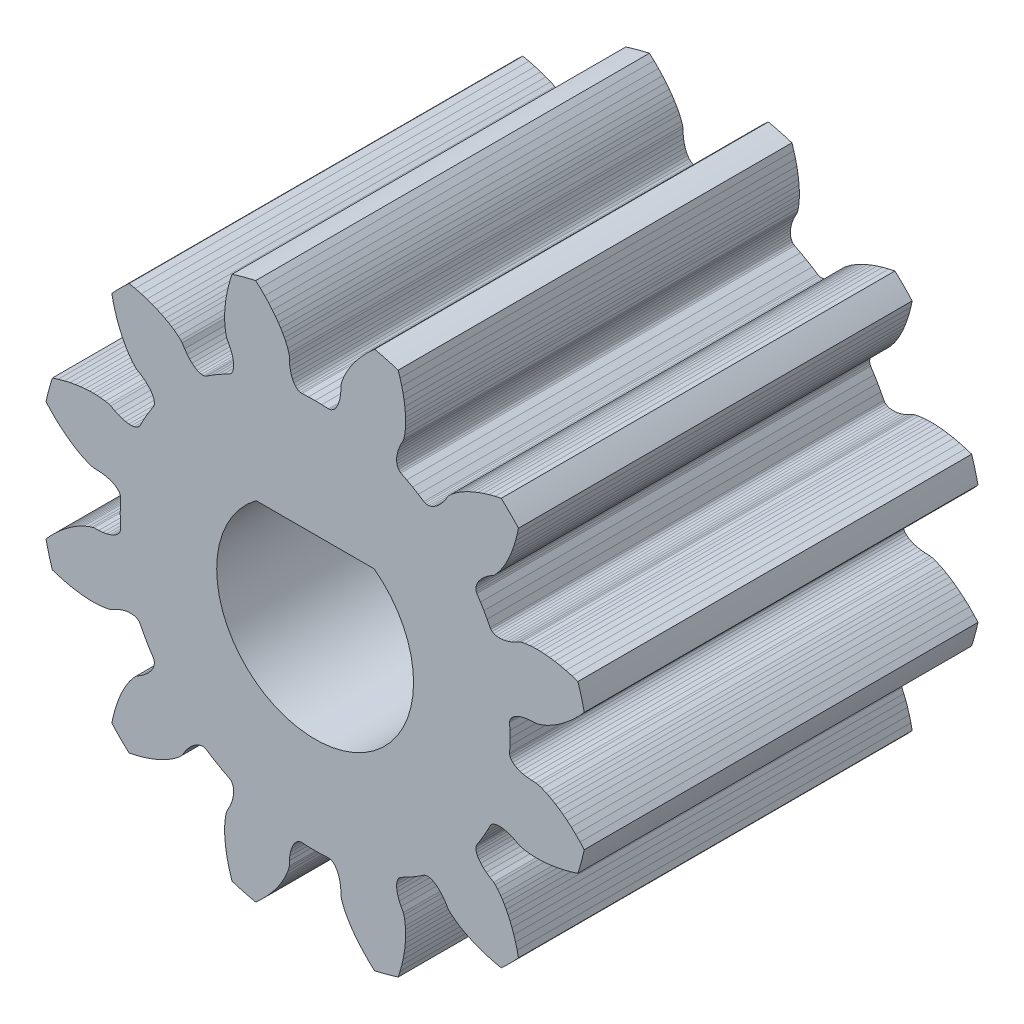
SolidWorks part; units mm, degrees
ref_plane "Front Plane" through (0, 0, 0) normal (0, 0, 1) x (1, 0, 0)
ref_plane "Top Plane" through (0, 0, 0) normal (0, 1, 0) x (1, 0, 0)
ref_plane "Right Plane" through (0, 0, 0) normal (1, 0, 0) x (0, 0, -1)
sketch "Model" plane through (0, 0, 0) normal (0, 0, 1) x (1, 0, 0)
  line L0 (30.8694, -4.5708) -> (30.9098, -4.4161)
  line L1 (30.9098, -4.4161) -> (30.9538, -4.2725)
  line L2 (30.9538, -4.2725) -> (31.0003, -4.1408)
  line L3 (31.0003, -4.1408) -> (31.0488, -4.0198)
  line L4 (31.0488, -4.0198) -> (31.0977, -3.9112)
  line L5 (31.0977, -3.9112) -> (31.1475, -3.8119)
  line L6 (31.1475, -3.8119) -> (31.1956, -3.7252)
  line L7 (31.1956, -3.7252) -> (31.2429, -3.6478)
  line L8 (31.2429, -3.6478) -> (31.2875, -3.5813)
  line L9 (31.2875, -3.5813) -> (31.3671, -3.477)
  line L10 (31.3671, -3.477) -> (31.4285, -3.4089)
  line L11 (31.4285, -3.4089) -> (31.466, -3.3746)
  line L12 (31.466, -3.3746) -> (31.5668, -3.3141)
  line L13 (31.5668, -3.3141) -> (31.6547, -3.2516)
  line L14 (31.6547, -3.2516) -> (31.7296, -3.1879)
  line L15 (31.7296, -3.1879) -> (31.7917, -3.1241)
  line L16 (31.7917, -3.1241) -> (31.841, -3.0611)
  line L17 (31.841, -3.0611) -> (31.8779, -2.9999)
  line L18 (31.8779, -2.9999) -> (31.9025, -2.9414)
  line L19 (31.9025, -2.9414) -> (31.9152, -2.8864)
  line L20 (31.9152, -2.8864) -> (31.9163, -2.836)
  line L21 (31.9163, -2.836) -> (31.9062, -2.7909)
  line L22 (31.9062, -2.7909) -> (31.8916, -2.7611)
  line L23 (31.8916, -2.7611) -> (31.8003, -2.6202)
  line L24 (31.8003, -2.6202) -> (31.7132, -2.475)
  line L25 (31.7132, -2.475) -> (31.631, -2.327)
  line L26 (31.631, -2.327) -> (31.5546, -2.1774)
  line L27 (31.5546, -2.1774) -> (31.5361, -2.1499)
  line L28 (31.5361, -2.1499) -> (31.5021, -2.1186)
  line L29 (31.5021, -2.1186) -> (31.4579, -2.0943)
  line L30 (31.4579, -2.0943) -> (31.404, -2.0778)
  line L31 (31.404, -2.0778) -> (31.341, -2.0699)
  line L32 (31.341, -2.0699) -> (31.2695, -2.0712)
  line L33 (31.2695, -2.0712) -> (31.1903, -2.0825)
  line L34 (31.1903, -2.0825) -> (31.104, -2.1043)
  line L35 (31.104, -2.1043) -> (31.0114, -2.1374)
  line L36 (31.0114, -2.1374) -> (30.9133, -2.1822)
  line L37 (30.9133, -2.1822) -> (30.8106, -2.2393)
  line L38 (30.8106, -2.2393) -> (30.762, -2.2546)
  line L39 (30.762, -2.2546) -> (30.6724, -2.2738)
  line L40 (30.6724, -2.2738) -> (30.5422, -2.2905)
  line L41 (30.5422, -2.2905) -> (30.4624, -2.2959)
  line L42 (30.4624, -2.2959) -> (30.3717, -2.2981)
  line L43 (30.3717, -2.2981) -> (30.2725, -2.2965)
  line L44 (30.2725, -2.2965) -> (30.1616, -2.2899)
  line L45 (30.1616, -2.2899) -> (30.0431, -2.278)
  line L46 (30.0431, -2.278) -> (29.9141, -2.2595)
  line L47 (29.9141, -2.2595) -> (29.7768, -2.2339)
  line L48 (29.7768, -2.2339) -> (29.6305, -2.2002)
  line L49 (29.6305, -2.2002) -> (29.4762, -2.1578)
  line L50 (29.4762, -2.1578) -> (29.3255, -2.1096)
  line L51 (29.1649, -1.5103) -> (29.2713, -1.3932)
  line L52 (29.2713, -1.3932) -> (29.3837, -1.2793)
  line L53 (29.3837, -1.2793) -> (29.4936, -1.177)
  line L54 (29.4936, -1.177) -> (29.5997, -1.0861)
  line L55 (29.5997, -1.0861) -> (29.7022, -1.0056)
  line L56 (29.7022, -1.0056) -> (29.7988, -0.9361)
  line L57 (29.7988, -0.9361) -> (29.8916, -0.875)
  line L58 (29.8916, -0.875) -> (29.9767, -0.8239)
  line L59 (29.9767, -0.8239) -> (30.0563, -0.7805)
  line L60 (30.0563, -0.7805) -> (30.1282, -0.7452)
  line L61 (30.1282, -0.7452) -> (30.2493, -0.6947)
  line L62 (30.2493, -0.6947) -> (30.3365, -0.6665)
  line L63 (30.3365, -0.6665) -> (30.3862, -0.6555)
  line L64 (30.3862, -0.6555) -> (30.5037, -0.6535)
  line L65 (30.5037, -0.6535) -> (30.611, -0.6433)
  line L66 (30.611, -0.6433) -> (30.7078, -0.6256)
  line L67 (30.7078, -0.6256) -> (30.7934, -0.6014)
  line L68 (30.7934, -0.6014) -> (30.8677, -0.5716)
  line L69 (30.8677, -0.5716) -> (30.9302, -0.537)
  line L70 (30.9302, -0.537) -> (30.9808, -0.4986)
  line L71 (30.9808, -0.4986) -> (31.0192, -0.4573)
  line L72 (31.0192, -0.4573) -> (31.0454, -0.4142)
  line L73 (31.0454, -0.4142) -> (31.0592, -0.3701)
  line L74 (31.0592, -0.3701) -> (31.0614, -0.337)
  line L75 (31.0614, -0.337) -> (31.0529, -0.1693)
  line L76 (31.0529, -0.1693) -> (31.05, 0)
  line L77 (31.05, 0) -> (31.0529, 0.1693)
  line L78 (31.0529, 0.1693) -> (31.0614, 0.337)
  line L79 (31.0614, 0.337) -> (31.0592, 0.3701)
  line L80 (31.0592, 0.3701) -> (31.0454, 0.4142)
  line L81 (31.0454, 0.4142) -> (31.0192, 0.4573)
  line L82 (31.0192, 0.4573) -> (30.9808, 0.4986)
  line L83 (30.9808, 0.4986) -> (30.9302, 0.537)
  line L84 (30.9302, 0.537) -> (30.8677, 0.5716)
  line L85 (30.8677, 0.5716) -> (30.7934, 0.6014)
  line L86 (30.7934, 0.6014) -> (30.7078, 0.6256)
  line L87 (30.7078, 0.6256) -> (30.611, 0.6433)
  line L88 (30.611, 0.6433) -> (30.5037, 0.6535)
  line L89 (30.5037, 0.6535) -> (30.3862, 0.6555)
  line L90 (30.3862, 0.6555) -> (30.3365, 0.6665)
  line L91 (30.3365, 0.6665) -> (30.2493, 0.6947)
  line L92 (30.2493, 0.6947) -> (30.1282, 0.7452)
  line L93 (30.1282, 0.7452) -> (30.0563, 0.7805)
  line L94 (30.0563, 0.7805) -> (29.9767, 0.8239)
  line L95 (29.9767, 0.8239) -> (29.8916, 0.875)
  line L96 (29.8916, 0.875) -> (29.7988, 0.9361)
  line L97 (29.7988, 0.9361) -> (29.7022, 1.0056)
  line L98 (29.7022, 1.0056) -> (29.5997, 1.0861)
  line L99 (29.5997, 1.0861) -> (29.4936, 1.177)
  line L100 (29.4936, 1.177) -> (29.3837, 1.2793)
  line L101 (29.3837, 1.2793) -> (29.2713, 1.3932)
  line L102 (29.2713, 1.3932) -> (29.1649, 1.5103)
  line L103 (29.3255, 2.1096) -> (29.4762, 2.1578)
  line L104 (29.4762, 2.1578) -> (29.6305, 2.2002)
  line L105 (29.6305, 2.2002) -> (29.7768, 2.2339)
  line L106 (29.7768, 2.2339) -> (29.9141, 2.2595)
  line L107 (29.9141, 2.2595) -> (30.0431, 2.278)
  line L108 (30.0431, 2.278) -> (30.1616, 2.2899)
  line L109 (30.1616, 2.2899) -> (30.2725, 2.2965)
  line L110 (30.2725, 2.2965) -> (30.3717, 2.2981)
  line L111 (30.3717, 2.2981) -> (30.4624, 2.2959)
  line L112 (30.4624, 2.2959) -> (30.5422, 2.2905)
  line L113 (30.5422, 2.2905) -> (30.6724, 2.2738)
  line L114 (30.6724, 2.2738) -> (30.762, 2.2546)
  line L115 (30.762, 2.2546) -> (30.8106, 2.2393)
  line L116 (30.8106, 2.2393) -> (30.9133, 2.1822)
  line L117 (30.9133, 2.1822) -> (31.0114, 2.1374)
  line L118 (31.0114, 2.1374) -> (31.104, 2.1043)
  line L119 (31.104, 2.1043) -> (31.1903, 2.0825)
  line L120 (31.1903, 2.0825) -> (31.2695, 2.0712)
  line L121 (31.2695, 2.0712) -> (31.341, 2.0699)
  line L122 (31.341, 2.0699) -> (31.404, 2.0778)
  line L123 (31.404, 2.0778) -> (31.4579, 2.0943)
  line L124 (31.4579, 2.0943) -> (31.5021, 2.1186)
  line L125 (31.5021, 2.1186) -> (31.5361, 2.1499)
  line L126 (31.5361, 2.1499) -> (31.5546, 2.1774)
  line L127 (31.5546, 2.1774) -> (31.631, 2.327)
  line L128 (31.631, 2.327) -> (31.7132, 2.475)
  line L129 (31.7132, 2.475) -> (31.8003, 2.6202)
  line L130 (31.8003, 2.6202) -> (31.8916, 2.7611)
  line L131 (31.8916, 2.7611) -> (31.9062, 2.7909)
  line L132 (31.9062, 2.7909) -> (31.9163, 2.836)
  line L133 (31.9163, 2.836) -> (31.9152, 2.8864)
  line L134 (31.9152, 2.8864) -> (31.9025, 2.9414)
  line L135 (31.9025, 2.9414) -> (31.8779, 2.9999)
  line L136 (31.8779, 2.9999) -> (31.841, 3.0611)
  line L137 (31.841, 3.0611) -> (31.7917, 3.1241)
  line L138 (31.7917, 3.1241) -> (31.7296, 3.1879)
  line L139 (31.7296, 3.1879) -> (31.6547, 3.2516)
  line L140 (31.6547, 3.2516) -> (31.5668, 3.3141)
  line L141 (31.5668, 3.3141) -> (31.466, 3.3746)
  line L142 (31.466, 3.3746) -> (31.4285, 3.4089)
  line L143 (31.4285, 3.4089) -> (31.3671, 3.477)
  line L144 (31.3671, 3.477) -> (31.2875, 3.5813)
  line L145 (31.2875, 3.5813) -> (31.2429, 3.6478)
  line L146 (31.2429, 3.6478) -> (31.1956, 3.7252)
  line L147 (31.1956, 3.7252) -> (31.1475, 3.8119)
  line L148 (31.1475, 3.8119) -> (31.0977, 3.9112)
  line L149 (31.0977, 3.9112) -> (31.0488, 4.0198)
  line L150 (31.0488, 4.0198) -> (31.0003, 4.1408)
  line L151 (31.0003, 4.1408) -> (30.9538, 4.2725)
  line L152 (30.9538, 4.2725) -> (30.9098, 4.4161)
  line L153 (30.9098, 4.4161) -> (30.8694, 4.5708)
  line L154 (30.8694, 4.5708) -> (30.8358, 4.7255)
  line L155 (31.2745, 5.1642) -> (31.4292, 5.1306)
  line L156 (31.4292, 5.1306) -> (31.5839, 5.0902)
  line L157 (31.5839, 5.0902) -> (31.7275, 5.0462)
  line L158 (31.7275, 5.0462) -> (31.8592, 4.9997)
  line L159 (31.8592, 4.9997) -> (31.9802, 4.9512)
  line L160 (31.9802, 4.9512) -> (32.0888, 4.9023)
  line L161 (32.0888, 4.9023) -> (32.1881, 4.8525)
  line L162 (32.1881, 4.8525) -> (32.2748, 4.8044)
  line L163 (32.2748, 4.8044) -> (32.3522, 4.7571)
  line L164 (32.3522, 4.7571) -> (32.4187, 4.7125)
  line L165 (32.4187, 4.7125) -> (32.523, 4.6329)
  line L166 (32.523, 4.6329) -> (32.5911, 4.5715)
  line L167 (32.5911, 4.5715) -> (32.6254, 4.534)
  line L168 (32.6254, 4.534) -> (32.6859, 4.4332)
  line L169 (32.6859, 4.4332) -> (32.7484, 4.3453)
  line L170 (32.7484, 4.3453) -> (32.8121, 4.2704)
  line L171 (32.8121, 4.2704) -> (32.8759, 4.2083)
  line L172 (32.8759, 4.2083) -> (32.9389, 4.159)
  line L173 (32.9389, 4.159) -> (33.0001, 4.1221)
  line L174 (33.0001, 4.1221) -> (33.0586, 4.0975)
  line L175 (33.0586, 4.0975) -> (33.1136, 4.0848)
  line L176 (33.1136, 4.0848) -> (33.164, 4.0837)
  line L177 (33.164, 4.0837) -> (33.2091, 4.0938)
  line L178 (33.2091, 4.0938) -> (33.2389, 4.1084)
  line L179 (33.2389, 4.1084) -> (33.3798, 4.1997)
  line L180 (33.3798, 4.1997) -> (33.525, 4.2868)
  line L181 (33.525, 4.2868) -> (33.673, 4.369)
  line L182 (33.673, 4.369) -> (33.8226, 4.4454)
  line L183 (33.8226, 4.4454) -> (33.8501, 4.4639)
  line L184 (33.8501, 4.4639) -> (33.8814, 4.4979)
  line L185 (33.8814, 4.4979) -> (33.9057, 4.5421)
  line L186 (33.9057, 4.5421) -> (33.9222, 4.596)
  line L187 (33.9222, 4.596) -> (33.9301, 4.659)
  line L188 (33.9301, 4.659) -> (33.9288, 4.7305)
  line L189 (33.9288, 4.7305) -> (33.9175, 4.8097)
  line L190 (33.9175, 4.8097) -> (33.8957, 4.896)
  line L191 (33.8957, 4.896) -> (33.8626, 4.9886)
  line L192 (33.8626, 4.9886) -> (33.8178, 5.0867)
  line L193 (33.8178, 5.0867) -> (33.7607, 5.1894)
  line L194 (33.7607, 5.1894) -> (33.7454, 5.238)
  line L195 (33.7454, 5.238) -> (33.7262, 5.3276)
  line L196 (33.7262, 5.3276) -> (33.7095, 5.4578)
  line L197 (33.7095, 5.4578) -> (33.7041, 5.5376)
  line L198 (33.7041, 5.5376) -> (33.7019, 5.6283)
  line L199 (33.7019, 5.6283) -> (33.7035, 5.7275)
  line L200 (33.7035, 5.7275) -> (33.7101, 5.8384)
  line L201 (33.7101, 5.8384) -> (33.722, 5.9569)
  line L202 (33.722, 5.9569) -> (33.7405, 6.0859)
  line L203 (33.7405, 6.0859) -> (33.7661, 6.2232)
  line L204 (33.7661, 6.2232) -> (33.7998, 6.3695)
  line L205 (33.7998, 6.3695) -> (33.8422, 6.5238)
  line L206 (33.8422, 6.5238) -> (33.8904, 6.6745)
  line L207 (34.4897, 6.8351) -> (34.6069, 6.7287)
  line L208 (34.6069, 6.7287) -> (34.7207, 6.6163)
  line L209 (34.7207, 6.6163) -> (34.823, 6.5064)
  line L210 (34.823, 6.5064) -> (34.9138, 6.4003)
  line L211 (34.9138, 6.4003) -> (34.9944, 6.2978)
  line L212 (34.9944, 6.2978) -> (35.0639, 6.2012)
  line L213 (35.0639, 6.2012) -> (35.125, 6.1084)
  line L214 (35.125, 6.1084) -> (35.1761, 6.0233)
  line L215 (35.1761, 6.0233) -> (35.2195, 5.9436)
  line L216 (35.2195, 5.9436) -> (35.2548, 5.8718)
  line L217 (35.2548, 5.8718) -> (35.3053, 5.7507)
  line L218 (35.3053, 5.7507) -> (35.3335, 5.6635)
  line L219 (35.3335, 5.6635) -> (35.3445, 5.6138)
  line L220 (35.3445, 5.6138) -> (35.3465, 5.4963)
  line L221 (35.3465, 5.4963) -> (35.3567, 5.389)
  line L222 (35.3567, 5.389) -> (35.3744, 5.2923)
  line L223 (35.3744, 5.2923) -> (35.3986, 5.2066)
  line L224 (35.3986, 5.2066) -> (35.4284, 5.1323)
  line L225 (35.4284, 5.1323) -> (35.463, 5.0698)
  line L226 (35.463, 5.0698) -> (35.5014, 5.0192)
  line L227 (35.5014, 5.0192) -> (35.5427, 4.9808)
  line L228 (35.5427, 4.9808) -> (35.5858, 4.9546)
  line L229 (35.5858, 4.9546) -> (35.6299, 4.9408)
  line L230 (35.6299, 4.9408) -> (35.663, 4.9386)
  line L231 (35.663, 4.9386) -> (35.8307, 4.9471)
  line L232 (35.8307, 4.9471) -> (36, 4.95)
  line L233 (36, 4.95) -> (36.1693, 4.9471)
  line L234 (36.1693, 4.9471) -> (36.337, 4.9386)
  line L235 (36.337, 4.9386) -> (36.3701, 4.9408)
  line L236 (36.3701, 4.9408) -> (36.4142, 4.9546)
  line L237 (36.4142, 4.9546) -> (36.4573, 4.9808)
  line L238 (36.4573, 4.9808) -> (36.4986, 5.0192)
  line L239 (36.4986, 5.0192) -> (36.537, 5.0698)
  line L240 (36.537, 5.0698) -> (36.5716, 5.1323)
  line L241 (36.5716, 5.1323) -> (36.6014, 5.2066)
  line L242 (36.6014, 5.2066) -> (36.6256, 5.2923)
  line L243 (36.6256, 5.2923) -> (36.6433, 5.389)
  line L244 (36.6433, 5.389) -> (36.6535, 5.4963)
  line L245 (36.6535, 5.4963) -> (36.6555, 5.6138)
  line L246 (36.6555, 5.6138) -> (36.6665, 5.6635)
  line L247 (36.6665, 5.6635) -> (36.6947, 5.7507)
  line L248 (36.6947, 5.7507) -> (36.7452, 5.8718)
  line L249 (36.7452, 5.8718) -> (36.7805, 5.9436)
  line L250 (36.7805, 5.9436) -> (36.8239, 6.0233)
  line L251 (36.8239, 6.0233) -> (36.875, 6.1084)
  line L252 (36.875, 6.1084) -> (36.9361, 6.2012)
  line L253 (36.9361, 6.2012) -> (37.0056, 6.2978)
  line L254 (37.0056, 6.2978) -> (37.0862, 6.4003)
  line L255 (37.0862, 6.4003) -> (37.177, 6.5064)
  line L256 (37.177, 6.5064) -> (37.2793, 6.6163)
  line L257 (37.2793, 6.6163) -> (37.3931, 6.7287)
  line L258 (37.3931, 6.7287) -> (37.5103, 6.8351)
  line L259 (38.1096, 6.6745) -> (38.1578, 6.5238)
  line L260 (38.1578, 6.5238) -> (38.2002, 6.3695)
  line L261 (38.2002, 6.3695) -> (38.2339, 6.2232)
  line L262 (38.2339, 6.2232) -> (38.2595, 6.0859)
  line L263 (38.2595, 6.0859) -> (38.278, 5.9569)
  line L264 (38.278, 5.9569) -> (38.2899, 5.8384)
  line L265 (38.2899, 5.8384) -> (38.2965, 5.7275)
  line L266 (38.2965, 5.7275) -> (38.2981, 5.6283)
  line L267 (38.2981, 5.6283) -> (38.2959, 5.5376)
  line L268 (38.2959, 5.5376) -> (38.2905, 5.4578)
  line L269 (38.2905, 5.4578) -> (38.2738, 5.3276)
  line L270 (38.2738, 5.3276) -> (38.2546, 5.238)
  line L271 (38.2546, 5.238) -> (38.2393, 5.1894)
  line L272 (38.2393, 5.1894) -> (38.1822, 5.0867)
  line L273 (38.1822, 5.0867) -> (38.1374, 4.9886)
  line L274 (38.1374, 4.9886) -> (38.1043, 4.896)
  line L275 (38.1043, 4.896) -> (38.0825, 4.8097)
  line L276 (38.0825, 4.8097) -> (38.0712, 4.7305)
  line L277 (38.0712, 4.7305) -> (38.0699, 4.659)
  line L278 (38.0699, 4.659) -> (38.0778, 4.596)
  line L279 (38.0778, 4.596) -> (38.0943, 4.5421)
  line L280 (38.0943, 4.5421) -> (38.1186, 4.4979)
  line L281 (38.1186, 4.4979) -> (38.1499, 4.4639)
  line L282 (38.1499, 4.4639) -> (38.1774, 4.4454)
  line L283 (38.1774, 4.4454) -> (38.327, 4.369)
  line L284 (38.327, 4.369) -> (38.475, 4.2868)
  line L285 (38.475, 4.2868) -> (38.6202, 4.1997)
  line L286 (38.6202, 4.1997) -> (38.7611, 4.1084)
  line L287 (38.7611, 4.1084) -> (38.7909, 4.0938)
  line L288 (38.7909, 4.0938) -> (38.836, 4.0837)
  line L289 (38.836, 4.0837) -> (38.8864, 4.0848)
  line L290 (38.8864, 4.0848) -> (38.9414, 4.0975)
  line L291 (38.9414, 4.0975) -> (38.9999, 4.1221)
  line L292 (38.9999, 4.1221) -> (39.0611, 4.159)
  line L293 (39.0611, 4.159) -> (39.1241, 4.2083)
  line L294 (39.1241, 4.2083) -> (39.1879, 4.2704)
  line L295 (39.1879, 4.2704) -> (39.2516, 4.3453)
  line L296 (39.2516, 4.3453) -> (39.3141, 4.4332)
  line L297 (39.3141, 4.4332) -> (39.3746, 4.534)
  line L298 (39.3746, 4.534) -> (39.4089, 4.5715)
  line L299 (39.4089, 4.5715) -> (39.477, 4.6329)
  line L300 (39.477, 4.6329) -> (39.5813, 4.7125)
  line L301 (39.5813, 4.7125) -> (39.6478, 4.7571)
  line L302 (39.6478, 4.7571) -> (39.7252, 4.8044)
  line L303 (39.7252, 4.8044) -> (39.8119, 4.8525)
  line L304 (39.8119, 4.8525) -> (39.9112, 4.9023)
  line L305 (39.9112, 4.9023) -> (40.0198, 4.9512)
  line L306 (40.0198, 4.9512) -> (40.1408, 4.9997)
  line L307 (40.1408, 4.9997) -> (40.2725, 5.0462)
  line L308 (40.2725, 5.0462) -> (40.4161, 5.0902)
  line L309 (40.4161, 5.0902) -> (40.5708, 5.1306)
  line L310 (40.5708, 5.1306) -> (40.7255, 5.1642)
  line L311 (41.1642, 4.7255) -> (41.1306, 4.5708)
  line L312 (41.1306, 4.5708) -> (41.0902, 4.4161)
  line L313 (41.0902, 4.4161) -> (41.0462, 4.2725)
  line L314 (41.0462, 4.2725) -> (40.9997, 4.1408)
  line L315 (40.9997, 4.1408) -> (40.9512, 4.0198)
  line L316 (40.9512, 4.0198) -> (40.9023, 3.9112)
  line L317 (40.9023, 3.9112) -> (40.8525, 3.8119)
  line L318 (40.8525, 3.8119) -> (40.8044, 3.7252)
  line L319 (40.8044, 3.7252) -> (40.7571, 3.6478)
  line L320 (40.7571, 3.6478) -> (40.7125, 3.5813)
  line L321 (40.7125, 3.5813) -> (40.6329, 3.477)
  line L322 (40.6329, 3.477) -> (40.5715, 3.4089)
  line L323 (40.5715, 3.4089) -> (40.534, 3.3746)
  line L324 (40.534, 3.3746) -> (40.4332, 3.3141)
  line L325 (40.4332, 3.3141) -> (40.3453, 3.2516)
  line L326 (40.3453, 3.2516) -> (40.2704, 3.1879)
  line L327 (40.2704, 3.1879) -> (40.2083, 3.1241)
  line L328 (40.2083, 3.1241) -> (40.159, 3.0611)
  line L329 (40.159, 3.0611) -> (40.1221, 2.9999)
  line L330 (40.1221, 2.9999) -> (40.0975, 2.9414)
  line L331 (40.0975, 2.9414) -> (40.0848, 2.8864)
  line L332 (40.0848, 2.8864) -> (40.0837, 2.836)
  line L333 (40.0837, 2.836) -> (40.0938, 2.7909)
  line L334 (40.0938, 2.7909) -> (40.1084, 2.7611)
  line L335 (40.1084, 2.7611) -> (40.1997, 2.6202)
  line L336 (40.1997, 2.6202) -> (40.2868, 2.475)
  line L337 (40.2868, 2.475) -> (40.369, 2.327)
  line L338 (40.369, 2.327) -> (40.4454, 2.1774)
  line L339 (40.4454, 2.1774) -> (40.4639, 2.1499)
  line L340 (40.4639, 2.1499) -> (40.4979, 2.1186)
  line L341 (40.4979, 2.1186) -> (40.5421, 2.0943)
  line L342 (40.5421, 2.0943) -> (40.596, 2.0778)
  line L343 (40.596, 2.0778) -> (40.659, 2.0699)
  line L344 (40.659, 2.0699) -> (40.7305, 2.0712)
  line L345 (40.7305, 2.0712) -> (40.8097, 2.0825)
  line L346 (40.8097, 2.0825) -> (40.896, 2.1043)
  line L347 (40.896, 2.1043) -> (40.9886, 2.1374)
  line L348 (40.9886, 2.1374) -> (41.0867, 2.1822)
  line L349 (41.0867, 2.1822) -> (41.1894, 2.2393)
  line L350 (41.1894, 2.2393) -> (41.238, 2.2546)
  line L351 (41.238, 2.2546) -> (41.3276, 2.2738)
  line L352 (41.3276, 2.2738) -> (41.4578, 2.2905)
  line L353 (41.4578, 2.2905) -> (41.5376, 2.2959)
  line L354 (41.5376, 2.2959) -> (41.6283, 2.2981)
  line L355 (41.6283, 2.2981) -> (41.7275, 2.2965)
  line L356 (41.7275, 2.2965) -> (41.8384, 2.2899)
  line L357 (41.8384, 2.2899) -> (41.9569, 2.278)
  line L358 (41.9569, 2.278) -> (42.0859, 2.2595)
  line L359 (42.0859, 2.2595) -> (42.2232, 2.2339)
  line L360 (42.2232, 2.2339) -> (42.3695, 2.2002)
  line L361 (42.3695, 2.2002) -> (42.5238, 2.1578)
  line L362 (42.5238, 2.1578) -> (42.6745, 2.1096)
  line L363 (42.8351, 1.5103) -> (42.7287, 1.3932)
  line L364 (42.7287, 1.3932) -> (42.6163, 1.2793)
  line L365 (42.6163, 1.2793) -> (42.5064, 1.177)
  line L366 (42.5064, 1.177) -> (42.4003, 1.0861)
  line L367 (42.4003, 1.0861) -> (42.2978, 1.0056)
  line L368 (42.2978, 1.0056) -> (42.2012, 0.9361)
  line L369 (42.2012, 0.9361) -> (42.1084, 0.875)
  line L370 (42.1084, 0.875) -> (42.0233, 0.8239)
  line L371 (42.0233, 0.8239) -> (41.9436, 0.7805)
  line L372 (41.9436, 0.7805) -> (41.8718, 0.7452)
  line L373 (41.8718, 0.7452) -> (41.7507, 0.6947)
  line L374 (41.7507, 0.6947) -> (41.6635, 0.6665)
  line L375 (41.6635, 0.6665) -> (41.6138, 0.6555)
  line L376 (41.6138, 0.6555) -> (41.4963, 0.6535)
  line L377 (41.4963, 0.6535) -> (41.389, 0.6433)
  line L378 (41.389, 0.6433) -> (41.2923, 0.6256)
  line L379 (41.2923, 0.6256) -> (41.2066, 0.6014)
  line L380 (41.2066, 0.6014) -> (41.1323, 0.5716)
  line L381 (41.1323, 0.5716) -> (41.0698, 0.537)
  line L382 (41.0698, 0.537) -> (41.0192, 0.4986)
  line L383 (41.0192, 0.4986) -> (40.9808, 0.4573)
  line L384 (40.9808, 0.4573) -> (40.9546, 0.4142)
  line L385 (40.9546, 0.4142) -> (40.9408, 0.3701)
  line L386 (40.9408, 0.3701) -> (40.9386, 0.337)
  line L387 (40.9386, 0.337) -> (40.9471, 0.1693)
  line L388 (40.9471, 0.1693) -> (40.95, 0)
  line L389 (40.95, 0) -> (40.9471, -0.1693)
  line L390 (40.9471, -0.1693) -> (40.9386, -0.337)
  line L391 (40.9386, -0.337) -> (40.9408, -0.3701)
  line L392 (40.9408, -0.3701) -> (40.9546, -0.4142)
  line L393 (40.9546, -0.4142) -> (40.9808, -0.4573)
  line L394 (40.9808, -0.4573) -> (41.0192, -0.4986)
  line L395 (41.0192, -0.4986) -> (41.0698, -0.537)
  line L396 (41.0698, -0.537) -> (41.1323, -0.5716)
  line L397 (41.1323, -0.5716) -> (41.2066, -0.6014)
  line L398 (41.2066, -0.6014) -> (41.2923, -0.6256)
  line L399 (41.2923, -0.6256) -> (41.389, -0.6433)
  line L400 (41.389, -0.6433) -> (41.4963, -0.6535)
  line L401 (41.4963, -0.6535) -> (41.6138, -0.6555)
  line L402 (41.6138, -0.6555) -> (41.6635, -0.6665)
  line L403 (41.6635, -0.6665) -> (41.7507, -0.6947)
  line L404 (41.7507, -0.6947) -> (41.8718, -0.7452)
  line L405 (41.8718, -0.7452) -> (41.9436, -0.7805)
  line L406 (41.9436, -0.7805) -> (42.0233, -0.8239)
  line L407 (42.0233, -0.8239) -> (42.1084, -0.875)
  line L408 (42.1084, -0.875) -> (42.2012, -0.9361)
  line L409 (42.2012, -0.9361) -> (42.2978, -1.0056)
  line L410 (42.2978, -1.0056) -> (42.4003, -1.0861)
  line L411 (42.4003, -1.0861) -> (42.5064, -1.177)
  line L412 (42.5064, -1.177) -> (42.6163, -1.2793)
  line L413 (42.6163, -1.2793) -> (42.7287, -1.3932)
  line L414 (42.7287, -1.3932) -> (42.8351, -1.5103)
  line L415 (42.6745, -2.1096) -> (42.5238, -2.1578)
  line L416 (42.5238, -2.1578) -> (42.3695, -2.2002)
  line L417 (42.3695, -2.2002) -> (42.2232, -2.2339)
  line L418 (42.2232, -2.2339) -> (42.0859, -2.2595)
  line L419 (42.0859, -2.2595) -> (41.9569, -2.278)
  line L420 (41.9569, -2.278) -> (41.8384, -2.2899)
  line L421 (41.8384, -2.2899) -> (41.7275, -2.2965)
  line L422 (41.7275, -2.2965) -> (41.6283, -2.2981)
  line L423 (41.6283, -2.2981) -> (41.5376, -2.2959)
  line L424 (41.5376, -2.2959) -> (41.4578, -2.2905)
  line L425 (41.4578, -2.2905) -> (41.3276, -2.2738)
  line L426 (41.3276, -2.2738) -> (41.238, -2.2546)
  line L427 (41.238, -2.2546) -> (41.1894, -2.2393)
  line L428 (41.1894, -2.2393) -> (41.0867, -2.1822)
  line L429 (41.0867, -2.1822) -> (40.9886, -2.1374)
  line L430 (40.9886, -2.1374) -> (40.896, -2.1043)
  line L431 (40.896, -2.1043) -> (40.8097, -2.0825)
  line L432 (40.8097, -2.0825) -> (40.7305, -2.0712)
  line L433 (40.7305, -2.0712) -> (40.659, -2.0699)
  line L434 (40.659, -2.0699) -> (40.596, -2.0778)
  line L435 (40.596, -2.0778) -> (40.5421, -2.0943)
  line L436 (40.5421, -2.0943) -> (40.4979, -2.1186)
  line L437 (40.4979, -2.1186) -> (40.4639, -2.1499)
  line L438 (40.4639, -2.1499) -> (40.4454, -2.1774)
  line L439 (40.4454, -2.1774) -> (40.369, -2.327)
  line L440 (40.369, -2.327) -> (40.2868, -2.475)
  line L441 (40.2868, -2.475) -> (40.1997, -2.6202)
  line L442 (40.1997, -2.6202) -> (40.1084, -2.7611)
  line L443 (40.1084, -2.7611) -> (40.0938, -2.7909)
  line L444 (40.0938, -2.7909) -> (40.0837, -2.836)
  line L445 (40.0837, -2.836) -> (40.0848, -2.8864)
  line L446 (40.0848, -2.8864) -> (40.0975, -2.9414)
  line L447 (40.0975, -2.9414) -> (40.1221, -2.9999)
  line L448 (40.1221, -2.9999) -> (40.159, -3.0611)
  line L449 (40.159, -3.0611) -> (40.2083, -3.1241)
  line L450 (40.2083, -3.1241) -> (40.2704, -3.1879)
  line L451 (40.2704, -3.1879) -> (40.3453, -3.2516)
  line L452 (40.3453, -3.2516) -> (40.4332, -3.3141)
  line L453 (40.4332, -3.3141) -> (40.534, -3.3746)
  line L454 (40.534, -3.3746) -> (40.5715, -3.4089)
  line L455 (40.5715, -3.4089) -> (40.6329, -3.477)
  line L456 (40.6329, -3.477) -> (40.7125, -3.5813)
  line L457 (40.7125, -3.5813) -> (40.7571, -3.6478)
  line L458 (40.7571, -3.6478) -> (40.8044, -3.7252)
  line L459 (40.8044, -3.7252) -> (40.8525, -3.8119)
  line L460 (40.8525, -3.8119) -> (40.9023, -3.9112)
  line L461 (40.9023, -3.9112) -> (40.9512, -4.0198)
  line L462 (40.9512, -4.0198) -> (40.9997, -4.1408)
  line L463 (40.9997, -4.1408) -> (41.0462, -4.2725)
  line L464 (41.0462, -4.2725) -> (41.0902, -4.4161)
  line L465 (41.0902, -4.4161) -> (41.1306, -4.5708)
  line L466 (41.1306, -4.5708) -> (41.1642, -4.7255)
  line L467 (40.7255, -5.1642) -> (40.5708, -5.1306)
  line L468 (40.5708, -5.1306) -> (40.4161, -5.0902)
  line L469 (40.4161, -5.0902) -> (40.2725, -5.0462)
  line L470 (40.2725, -5.0462) -> (40.1408, -4.9997)
  line L471 (40.1408, -4.9997) -> (40.0198, -4.9512)
  line L472 (40.0198, -4.9512) -> (39.9112, -4.9023)
  line L473 (39.9112, -4.9023) -> (39.8119, -4.8525)
  line L474 (39.8119, -4.8525) -> (39.7252, -4.8044)
  line L475 (39.7252, -4.8044) -> (39.6478, -4.7571)
  line L476 (39.6478, -4.7571) -> (39.5813, -4.7125)
  line L477 (39.5813, -4.7125) -> (39.477, -4.6329)
  line L478 (39.477, -4.6329) -> (39.4089, -4.5715)
  line L479 (39.4089, -4.5715) -> (39.3746, -4.534)
  line L480 (39.3746, -4.534) -> (39.3141, -4.4332)
  line L481 (39.3141, -4.4332) -> (39.2516, -4.3453)
  line L482 (39.2516, -4.3453) -> (39.1879, -4.2704)
  line L483 (39.1879, -4.2704) -> (39.1241, -4.2083)
  line L484 (39.1241, -4.2083) -> (39.0611, -4.159)
  line L485 (39.0611, -4.159) -> (38.9999, -4.1221)
  line L486 (38.9999, -4.1221) -> (38.9414, -4.0975)
  line L487 (38.9414, -4.0975) -> (38.8864, -4.0848)
  line L488 (38.8864, -4.0848) -> (38.836, -4.0837)
  line L489 (38.836, -4.0837) -> (38.7909, -4.0938)
  line L490 (38.7909, -4.0938) -> (38.7611, -4.1084)
  line L491 (38.7611, -4.1084) -> (38.6202, -4.1997)
  line L492 (38.6202, -4.1997) -> (38.475, -4.2868)
  line L493 (38.475, -4.2868) -> (38.327, -4.369)
  line L494 (38.327, -4.369) -> (38.1774, -4.4454)
  line L495 (38.1774, -4.4454) -> (38.1499, -4.4639)
  line L496 (38.1499, -4.4639) -> (38.1186, -4.4979)
  line L497 (38.1186, -4.4979) -> (38.0943, -4.5421)
  line L498 (38.0943, -4.5421) -> (38.0778, -4.596)
  line L499 (38.0778, -4.596) -> (38.0699, -4.659)
  line L500 (38.0699, -4.659) -> (38.0712, -4.7305)
  line L501 (38.0712, -4.7305) -> (38.0825, -4.8097)
  line L502 (38.0825, -4.8097) -> (38.1043, -4.896)
  line L503 (38.1043, -4.896) -> (38.1374, -4.9886)
  line L504 (38.1374, -4.9886) -> (38.1822, -5.0867)
  line L505 (38.1822, -5.0867) -> (38.2393, -5.1894)
  line L506 (38.2393, -5.1894) -> (38.2546, -5.238)
  line L507 (38.2546, -5.238) -> (38.2738, -5.3276)
  line L508 (38.2738, -5.3276) -> (38.2905, -5.4578)
  line L509 (38.2905, -5.4578) -> (38.2959, -5.5376)
  line L510 (38.2959, -5.5376) -> (38.2981, -5.6283)
  line L511 (38.2981, -5.6283) -> (38.2965, -5.7275)
  line L512 (38.2965, -5.7275) -> (38.2899, -5.8384)
  line L513 (38.2899, -5.8384) -> (38.278, -5.9569)
  line L514 (38.278, -5.9569) -> (38.2595, -6.0859)
  line L515 (38.2595, -6.0859) -> (38.2339, -6.2232)
  line L516 (38.2339, -6.2232) -> (38.2002, -6.3695)
  line L517 (38.2002, -6.3695) -> (38.1578, -6.5238)
  line L518 (38.1578, -6.5238) -> (38.1096, -6.6745)
  line L519 (37.5103, -6.8351) -> (37.3931, -6.7287)
  line L520 (37.3931, -6.7287) -> (37.2793, -6.6163)
  line L521 (37.2793, -6.6163) -> (37.177, -6.5064)
  line L522 (37.177, -6.5064) -> (37.0862, -6.4003)
  line L523 (37.0862, -6.4003) -> (37.0056, -6.2978)
  line L524 (37.0056, -6.2978) -> (36.9361, -6.2012)
  line L525 (36.9361, -6.2012) -> (36.875, -6.1084)
  line L526 (36.875, -6.1084) -> (36.8239, -6.0233)
  line L527 (36.8239, -6.0233) -> (36.7805, -5.9436)
  line L528 (36.7805, -5.9436) -> (36.7452, -5.8718)
  line L529 (36.7452, -5.8718) -> (36.6947, -5.7507)
  line L530 (36.6947, -5.7507) -> (36.6665, -5.6635)
  line L531 (36.6665, -5.6635) -> (36.6555, -5.6138)
  line L532 (36.6555, -5.6138) -> (36.6535, -5.4963)
  line L533 (36.6535, -5.4963) -> (36.6433, -5.389)
  line L534 (36.6433, -5.389) -> (36.6256, -5.2923)
  line L535 (36.6256, -5.2923) -> (36.6014, -5.2066)
  line L536 (36.6014, -5.2066) -> (36.5716, -5.1323)
  line L537 (36.5716, -5.1323) -> (36.537, -5.0698)
  line L538 (36.537, -5.0698) -> (36.4986, -5.0192)
  line L539 (36.4986, -5.0192) -> (36.4573, -4.9808)
  line L540 (36.4573, -4.9808) -> (36.4142, -4.9546)
  line L541 (36.4142, -4.9546) -> (36.3701, -4.9408)
  line L542 (36.3701, -4.9408) -> (36.337, -4.9386)
  line L543 (36.337, -4.9386) -> (36.1693, -4.9471)
  line L544 (36.1693, -4.9471) -> (36, -4.95)
  line L545 (36, -4.95) -> (35.8307, -4.9471)
  line L546 (35.8307, -4.9471) -> (35.663, -4.9386)
  line L547 (35.663, -4.9386) -> (35.6299, -4.9408)
  line L548 (35.6299, -4.9408) -> (35.5858, -4.9546)
  line L549 (35.5858, -4.9546) -> (35.5427, -4.9808)
  line L550 (35.5427, -4.9808) -> (35.5014, -5.0192)
  line L551 (35.5014, -5.0192) -> (35.463, -5.0698)
  line L552 (35.463, -5.0698) -> (35.4284, -5.1323)
  line L553 (35.4284, -5.1323) -> (35.3986, -5.2066)
  line L554 (35.3986, -5.2066) -> (35.3744, -5.2923)
  line L555 (35.3744, -5.2923) -> (35.3567, -5.389)
  line L556 (35.3567, -5.389) -> (35.3465, -5.4963)
  line L557 (35.3465, -5.4963) -> (35.3445, -5.6138)
  line L558 (35.3445, -5.6138) -> (35.3335, -5.6635)
  line L559 (35.3335, -5.6635) -> (35.3053, -5.7507)
  line L560 (35.3053, -5.7507) -> (35.2548, -5.8718)
  line L561 (35.2548, -5.8718) -> (35.2195, -5.9436)
  line L562 (35.2195, -5.9436) -> (35.1761, -6.0233)
  line L563 (35.1761, -6.0233) -> (35.125, -6.1084)
  line L564 (35.125, -6.1084) -> (35.0639, -6.2012)
  line L565 (35.0639, -6.2012) -> (34.9944, -6.2978)
  line L566 (34.9944, -6.2978) -> (34.9138, -6.4003)
  line L567 (34.9138, -6.4003) -> (34.823, -6.5064)
  line L568 (34.823, -6.5064) -> (34.7207, -6.6163)
  line L569 (34.7207, -6.6163) -> (34.6069, -6.7287)
  line L570 (34.6069, -6.7287) -> (34.4897, -6.8351)
  line L571 (33.8904, -6.6745) -> (33.8422, -6.5238)
  line L572 (33.8422, -6.5238) -> (33.7998, -6.3695)
  line L573 (33.7998, -6.3695) -> (33.7661, -6.2232)
  line L574 (33.7661, -6.2232) -> (33.7405, -6.0859)
  line L575 (33.7405, -6.0859) -> (33.722, -5.9569)
  line L576 (33.722, -5.9569) -> (33.7101, -5.8384)
  line L577 (33.7101, -5.8384) -> (33.7035, -5.7275)
  line L578 (33.7035, -5.7275) -> (33.7019, -5.6283)
  line L579 (33.7019, -5.6283) -> (33.7041, -5.5376)
  line L580 (33.7041, -5.5376) -> (33.7095, -5.4578)
  line L581 (33.7095, -5.4578) -> (33.7262, -5.3276)
  line L582 (33.7262, -5.3276) -> (33.7454, -5.238)
  line L583 (33.7454, -5.238) -> (33.7607, -5.1894)
  line L584 (33.7607, -5.1894) -> (33.8178, -5.0867)
  line L585 (33.8178, -5.0867) -> (33.8626, -4.9886)
  line L586 (33.8626, -4.9886) -> (33.8957, -4.896)
  line L587 (33.8957, -4.896) -> (33.9175, -4.8097)
  line L588 (33.9175, -4.8097) -> (33.9288, -4.7305)
  line L589 (33.9288, -4.7305) -> (33.9301, -4.659)
  line L590 (33.9301, -4.659) -> (33.9222, -4.596)
  line L591 (33.9222, -4.596) -> (33.9057, -4.5421)
  line L592 (33.9057, -4.5421) -> (33.8814, -4.4979)
  line L593 (33.8814, -4.4979) -> (33.8501, -4.4639)
  line L594 (33.8501, -4.4639) -> (33.8226, -4.4454)
  line L595 (33.8226, -4.4454) -> (33.673, -4.369)
  line L596 (33.673, -4.369) -> (33.525, -4.2868)
  line L597 (33.525, -4.2868) -> (33.3798, -4.1997)
  line L598 (33.3798, -4.1997) -> (33.2389, -4.1084)
  line L599 (33.2389, -4.1084) -> (33.2091, -4.0938)
  line L600 (33.2091, -4.0938) -> (33.164, -4.0837)
  line L601 (33.164, -4.0837) -> (33.1136, -4.0848)
  line L602 (33.1136, -4.0848) -> (33.0586, -4.0975)
  line L603 (33.0586, -4.0975) -> (33.0001, -4.1221)
  line L604 (33.0001, -4.1221) -> (32.9389, -4.159)
  line L605 (32.9389, -4.159) -> (32.8759, -4.2083)
  line L606 (32.8759, -4.2083) -> (32.8121, -4.2704)
  line L607 (32.8121, -4.2704) -> (32.7484, -4.3453)
  line L608 (32.7484, -4.3453) -> (32.6859, -4.4332)
  line L609 (32.6859, -4.4332) -> (32.6254, -4.534)
  line L610 (32.6254, -4.534) -> (32.5911, -4.5715)
  line L611 (32.5911, -4.5715) -> (32.523, -4.6329)
  line L612 (32.523, -4.6329) -> (32.4187, -4.7125)
  line L613 (32.4187, -4.7125) -> (32.3522, -4.7571)
  line L614 (32.3522, -4.7571) -> (32.2748, -4.8044)
  line L615 (32.2748, -4.8044) -> (32.1881, -4.8525)
  line L616 (32.1881, -4.8525) -> (32.0888, -4.9023)
  line L617 (32.0888, -4.9023) -> (31.9802, -4.9512)
  line L618 (31.9802, -4.9512) -> (31.8592, -4.9997)
  line L619 (31.8592, -4.9997) -> (31.7275, -5.0462)
  line L620 (31.7275, -5.0462) -> (31.5839, -5.0902)
  line L621 (31.5839, -5.0902) -> (31.4292, -5.1306)
  line L622 (31.4292, -5.1306) -> (31.2745, -5.1642)
  line L623 (30.8358, -4.7255) -> (30.8694, -4.5708)
  circle A1 centre (36, 0) radius 2.5
  arc A2 (29.1649, -1.5103) -> (29.3255, -2.1096) centre (36, 0) ccw
  arc A3 (29.3255, 2.1096) -> (29.1649, 1.5103) centre (36, 0) ccw
  arc A4 (31.2745, 5.1642) -> (30.8358, 4.7255) centre (36, 0) ccw
  arc A5 (34.4897, 6.8351) -> (33.8904, 6.6745) centre (36, 0) ccw
  arc A6 (38.1096, 6.6745) -> (37.5103, 6.8351) centre (36, 0) ccw
  arc A7 (41.1642, 4.7255) -> (40.7255, 5.1642) centre (36, 0) ccw
  arc A8 (42.8351, 1.5103) -> (42.6745, 2.1096) centre (36, 0) ccw
  arc A9 (42.6745, -2.1096) -> (42.8351, -1.5103) centre (36, 0) ccw
  arc A10 (40.7255, -5.1642) -> (41.1642, -4.7255) centre (36, 0) ccw
  arc A11 (37.5103, -6.8351) -> (38.1096, -6.6745) centre (36, 0) ccw
  arc A12 (33.8904, -6.6745) -> (34.4897, -6.8351) centre (36, 0) ccw
  arc A13 (30.8358, -4.7255) -> (31.2745, -5.1642) centre (36, 0) ccw
extrude "Boss-Extrude1" add sketch "Model" along normal blind 10
sketch "Sketch2" plane through (0, 0, 10) normal (0, 0, 1) x (1, 0, 0)
  line L1 (33.184, 3.5143) -> (38.8387, 3.5143)
  line L2 (33.184, 3.5143) -> (33.184, 2)
  line L3 (33.184, 2) -> (38.8387, 2)
  line L4 (38.8387, 3.5143) -> (38.8387, 2)
  circle A0 centre (36, 0) radius 2.5 construction
  arc A1 (29.3255, 2.1096) -> (29.1649, 1.5103) centre (36, 0) ccw construction
  arc A2 (41.1642, 4.7255) -> (40.7255, 5.1642) centre (36, 0) ccw construction
  dimension "D1" = 4.5
  dimension "D2" = 1.5143
  dimension "D3" = 2.816
  dimension "D4" = 2.8387
extrude "Boss-Extrude2" add sketch "Sketch2" against normal blind 10
